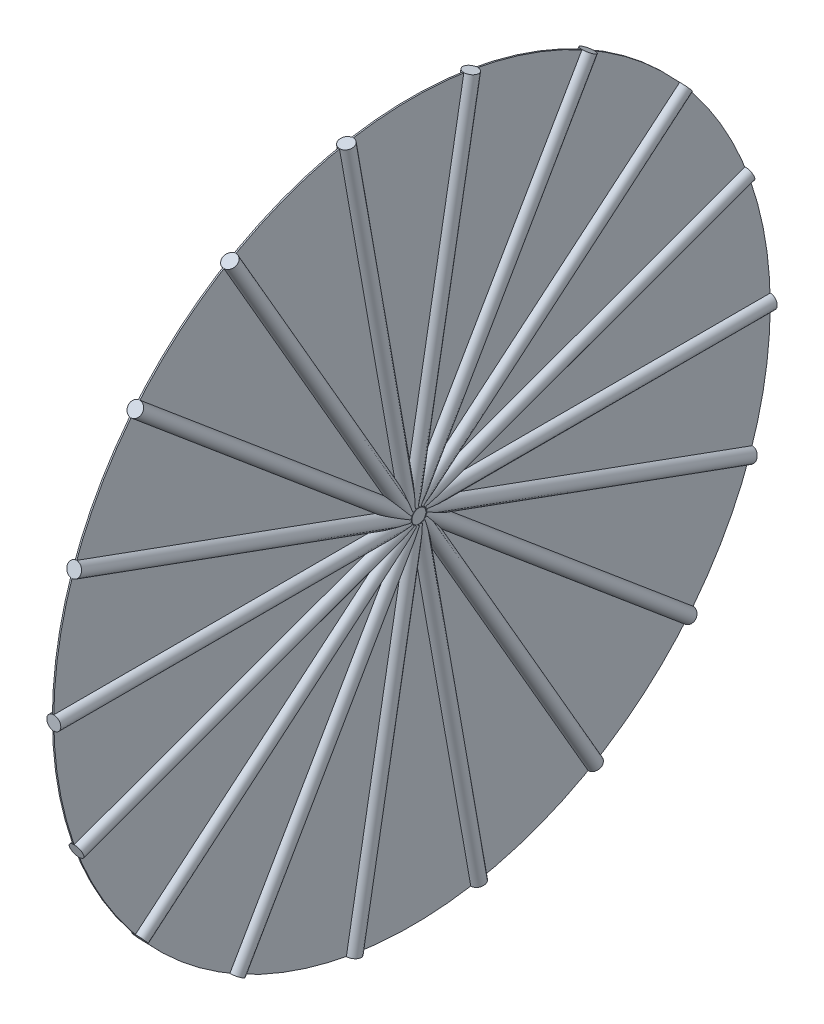
SolidWorks part; units mm, degrees
material "Glass"
ref_plane "Front Plane" through (0, 0, 0) normal (0, 0, 1) x (1, 0, 0)
ref_plane "Top Plane" through (0, 0, 0) normal (0, 1, 0) x (1, 0, 0)
ref_plane "Right Plane" through (0, 0, 0) normal (1, 0, 0) x (0, 0, -1)
sketch "Sketch3" plane through (39.7843, 0, 0) normal (0, 0, 1) x (1, 0, 0)
  line L1 (0, 0) -> (25, 0)
  line L2 (0, 0) -> (0, 25.4)
  line L3 (0, 25.4) -> (25, 25.4)
  line L4 (25, 0) -> (25, 25.4)
  point P4 (5.3277, 0)
  point P5 (0, 0)
revolve "Revolve2" add sketch "Sketch3" angle 360 about L1
sketch "Sketch6" plane through (39.7843, 0, 0) normal (-1, 0, 0) x (0, 0, 1)
  line L1 (25.4, -12.7) -> (1300, -12.7)
  line L2 (25.4, -12.7) -> (25.4, 12.7)
  line L3 (25.4, 12.7) -> (1300, 12.7)
  line L4 (1300, -12.7) -> (1300, 12.7)
revolve "Revolve3" add sketch "Sketch6" angle 360 about L1
sketch "Sketch7" plane through (39.7843, 0, 0) normal (-1, 0, 0) x (0, 0, 1)
  circle A0 centre (0, 0) radius 1300
extrude "Boss-Extrude2" add sketch "Sketch7" along normal blind 5.08
pattern_circular "CirPattern1" count 18 over 360 about axis through (34.7043, 0, 0) along (-1, 0, 0) of "Revolve3"
